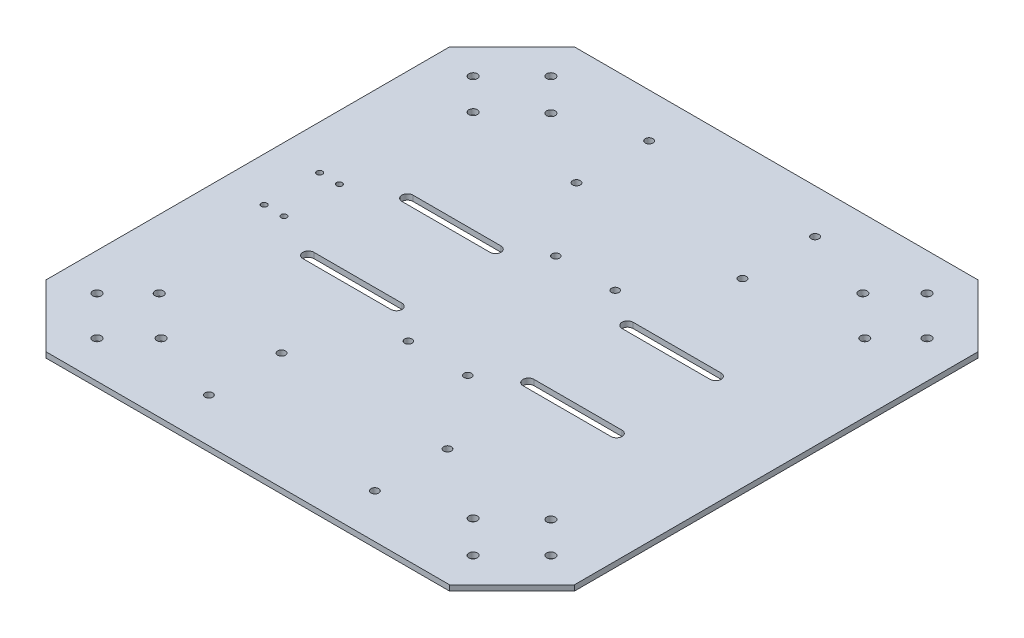
SolidWorks part; units mm, degrees
ref_plane "Front Plane" through (0, 0, 0) normal (0, 0, 1) x (1, 0, 0)
ref_plane "Top Plane" through (0, 0, 0) normal (0, 1, 0) x (1, 0, 0)
ref_plane "Right Plane" through (0, 0, 0) normal (1, 0, 0) x (0, 0, -1)
sketch "Sketch1" plane through (0, 0, 0) normal (0, 1, 0) x (1, 0, 0)
  line L0 (-61.766, 15.7353) -> (-25.845, 51.6564)
  line L1 (-61.766, 51.6564) -> (243.034, 51.6564)
  line L2 (-61.766, 51.6564) -> (-61.766, -253.1436)
  line L3 (-61.766, -253.1436) -> (243.034, -253.1436)
  line L4 (243.034, 51.6564) -> (243.034, -253.1436)
  line L5 (90.634, 95.069) -> (90.634, -294.9418) construction
  line L6 (-86.5248, -100.7436) -> (277.558, -100.7436) construction
  line L7 (243.034, 15.7353) -> (207.1129, 51.6564)
  line L8 (243.034, -217.2226) -> (207.1129, -253.1436)
  line L9 (-61.766, -217.2226) -> (-25.845, -253.1436)
  line L10 (128.734, -72.1686) -> (179.534, -72.1686) construction
  line L11 (128.734, -68.9936) -> (179.534, -68.9936)
  line L12 (128.734, -75.3436) -> (179.534, -75.3436)
  line L13 (128.734, -129.3186) -> (179.534, -129.3186) construction
  line L14 (128.734, -132.4936) -> (179.534, -132.4936)
  line L15 (128.734, -126.1436) -> (179.534, -126.1436)
  line L16 (52.534, -129.3186) -> (1.734, -129.3186) construction
  line L17 (52.534, -132.4936) -> (1.734, -132.4936)
  line L18 (52.534, -126.1436) -> (1.734, -126.1436)
  line L19 (52.534, -72.1686) -> (1.734, -72.1686) construction
  line L20 (52.534, -68.9936) -> (1.734, -68.9936)
  line L21 (52.534, -75.3436) -> (1.734, -75.3436)
  arc A0 (128.734, -68.9936) -> (128.734, -75.3436) centre (128.734, -72.1686) ccw
  arc A1 (179.534, -75.3436) -> (179.534, -68.9936) centre (179.534, -72.1686) ccw
  arc A2 (128.734, -132.4936) -> (128.734, -126.1436) centre (128.734, -129.3186) cw
  arc A3 (179.534, -126.1436) -> (179.534, -132.4936) centre (179.534, -129.3186) cw
  arc A4 (52.534, -132.4936) -> (52.534, -126.1436) centre (52.534, -129.3186) ccw
  arc A5 (1.734, -126.1436) -> (1.734, -132.4936) centre (1.734, -129.3186) ccw
  arc A6 (52.534, -68.9936) -> (52.534, -75.3436) centre (52.534, -72.1686) cw
  arc A7 (1.734, -75.3436) -> (1.734, -68.9936) centre (1.734, -72.1686) cw
  point P8 (90.634, 51.6564)
  point P11 (-61.766, -100.7436)
  point P18 (154.134, -72.1686)
  point P27 (154.134, -129.3186)
  point P34 (27.134, -129.3186)
  point P41 (27.134, -72.1686)
  point P46 (0, 0)
  point P47 (0, 0)
  dimension "D6" = 6.35
  dimension "D1" = 304.8
  dimension "D2" = 304.8
  dimension "D3" = 45
  dimension "D4" = 50.8
  dimension "D5" = 50.8
  dimension "D7" = 38.1
  dimension "D8" = 50.8
extrude "Boss-Extrude1" add sketch "Sketch1" along normal blind 3.175 contours L2 L9 L3 L8 L4 L7 L1 L0 A5 L18 A4 L17 A1 L12 A0 L11 L15 A3 L14 A2 L21 A7 L20 A6 region at (90.634, 0, 100.7436)
sketch "Sketch2" plane through (0, 3.175, 0) normal (0, 1, 0) x (1, 0, 0)
  line L0 (-40.323, 7.7627) -> (-22.3625, -10.1978) construction
  line L1 (-17.8724, 30.2133) -> (0.6409, 11.7001) construction
  line L2 (-43.8055, 33.6958) -> (20.8232, -30.9329) construction
  line L3 (-61.766, 15.7353) -> (-25.845, 51.6564) construction
  line L7 (90.634, 51.6564) -> (90.634, -253.1436) construction
  line L8 (-25.845, 51.6564) -> (207.1129, 51.6564) construction
  line L9 (-25.845, -253.1436) -> (207.1129, -253.1436) construction
  line L10 (-61.766, -100.7436) -> (243.034, -100.7436) construction
  line L11 (-61.766, 15.7353) -> (-61.766, -217.2226) construction
  line L12 (243.034, 15.7353) -> (243.034, -217.2226) construction
  circle A0 centre (-17.8724, 30.2133) radius 2.4638
  circle A1 centre (0.6409, 11.7001) radius 2.4638
  circle A2 centre (-22.3625, -10.1978) radius 2.4638
  circle A3 centre (-40.323, 7.7627) radius 2.4638
  circle A4 centre (203.6304, -10.1978) radius 2.4638
  circle A5 centre (221.5909, 7.7627) radius 2.4638
  circle A6 centre (180.627, 11.7001) radius 2.4638
  circle A7 centre (199.1403, 30.2133) radius 2.4638
  circle A8 centre (-22.3625, -191.2895) radius 2.4638
  circle A9 centre (-40.323, -209.25) radius 2.4638
  circle A10 centre (-17.8724, -231.7006) radius 2.4638
  circle A11 centre (0.6409, -213.1873) radius 2.4638
  circle A12 centre (221.5909, -209.25) radius 2.4638
  circle A13 centre (199.1403, -231.7006) radius 2.4638
  circle A14 centre (180.627, -213.1873) radius 2.4638
  circle A15 centre (203.6304, -191.2895) radius 2.4638
  dimension "D3" = 4.9276
  dimension "D4" = 4.9276
  dimension "D5" = 4.9276
  dimension "D6" = 4.9276
  dimension "D1" = 25.4
  dimension "D2" = 31.75
  dimension "D7" = 15.875
extrude "Cut-Extrude1" cut sketch "Sketch2" against normal blind 6.35
sketch "Sketch3" plane through (0, 3.175, 0) normal (0, 1, 0) x (1, 0, 0)
  line L0 (-61.766, -100.7436) -> (278.5513, -100.7436) construction
  line L2 (-61.766, 15.7353) -> (-61.766, -217.2226) construction
  line L3 (90.634, 51.6564) -> (90.634, -273.1997) construction
  line L4 (-25.845, 51.6564) -> (207.1129, 51.6564) construction
  circle A0 centre (73.362, -58.1986) radius 2.159
  circle A1 centre (107.652, -58.1986) radius 2.159
  circle A2 centre (73.362, -143.2886) radius 2.159
  circle A3 centre (107.652, -143.2886) radius 2.159
  point P10 (-61.766, -100.7436)
  point P17 (0, 0)
  point P18 (0, 0)
  dimension "D3" = 4.318
  dimension "D4" = 4.318
  dimension "D5" = 4.318
  dimension "D6" = 4.318
  dimension "D1" = 34.29
  dimension "D2" = 85.09
  dimension "D7" = 42.545
  dimension "D8" = 17.272
extrude "Cut-Extrude2" cut sketch "Sketch3" against normal blind 6.35
sketch "Sketch4" plane through (0, 3.175, 0) normal (0, 1, 0) x (1, 0, 0)
  line L0 (90.634, 51.6564) -> (90.634, -36.4614) construction
  line L1 (-25.845, 51.6564) -> (207.1129, 51.6564) construction
  line L2 (-61.766, -100.7436) -> (257.447, -100.7436) construction
  line L3 (-61.766, 15.7353) -> (-61.766, -217.2226) construction
  circle A0 centre (42.755, 26.2564) radius 2.2225
  circle A1 centre (138.513, 26.2564) radius 2.2225
  circle A2 centre (42.755, -15.6536) radius 2.2225
  circle A3 centre (138.513, -15.6536) radius 2.2225
  circle A4 centre (138.513, -185.8336) radius 2.2225
  circle A5 centre (42.755, -185.8336) radius 2.2225
  circle A6 centre (138.513, -227.7436) radius 2.2225
  circle A7 centre (42.755, -227.7436) radius 2.2225
  point P12 (0, 0)
  dimension "D1" = 4.445
  dimension "D2" = 4.445
  dimension "D3" = 4.445
  dimension "D4" = 4.445
  dimension "D5" = 95.758
  dimension "D6" = 41.91
  dimension "D7" = 47.879
  dimension "D8" = 25.4
extrude "Cut-Extrude3" cut sketch "Sketch4" against normal through all
sketch "Sketch5" plane through (0, 3.175, 0) normal (0, 1, 0) x (1, 0, 0)
  line L0 (-61.766, -100.7436) -> (105.2484, -100.7436) construction
  line L1 (-61.766, 15.7353) -> (-61.766, -217.2226) construction
  circle A0 centre (-36.366, -84.7416) radius 1.651
  circle A1 centre (-24.936, -84.7416) radius 1.651
  circle A2 centre (-24.936, -116.7456) radius 1.651
  circle A3 centre (-36.366, -116.7456) radius 1.651
  dimension "D1" = 3.302
  dimension "D2" = 3.302
  dimension "D3" = 11.43
  dimension "D4" = 16.002
  dimension "D5" = 25.4
extrude "Cut-Extrude4" cut sketch "Sketch5" against normal through all
